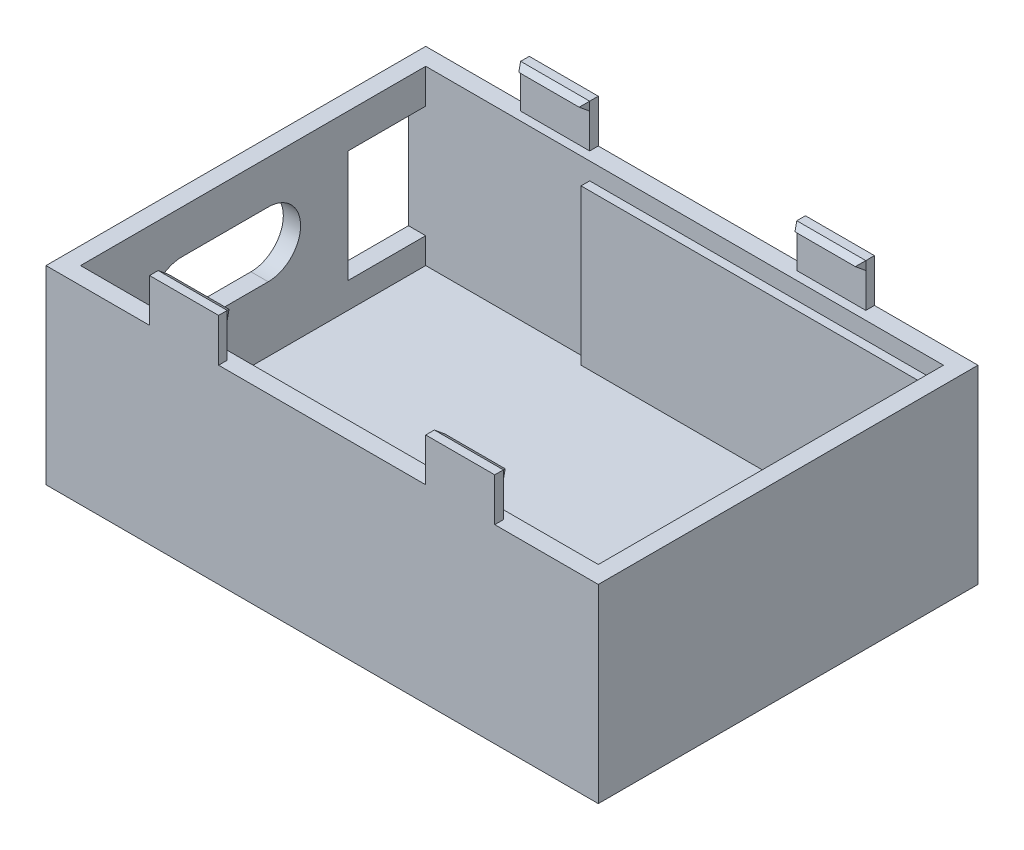
SolidWorks part; units mm, degrees
ref_plane "Front Plane" through (0, 0, 0) normal (0, 0, 1) x (1, 0, 0)
ref_plane "Top Plane" through (0, 0, 0) normal (0, 1, 0) x (1, 0, 0)
ref_plane "Right Plane" through (0, 0, 0) normal (1, 0, 0) x (0, 0, -1)
sketch "Sketch3" plane through (0, 0, 0) normal (0, 1, 0) x (1, 0, 0)
  line L9 (-32, 22) -> (32, 22)
  line L10 (-32, 22) -> (-32, -22)
  line L11 (-32, -22) -> (32, -22)
  line L12 (32, 22) -> (32, -22)
  line L13 (-32, 22) -> (32, -22) construction
  line L14 (-32, -22) -> (32, 22) construction
  line L15 (-30, 20) -> (-11, 20)
  line L16 (-30, 20) -> (-30, -20)
  line L17 (-30, -20) -> (29, -20)
  line L19 (-30, 20) -> (29, -19.3333) construction
  line L20 (-30, -20) -> (29.0678, 19.3785) construction
  line L22 (-11, 20) -> (-11, 19)
  line L23 (-11, 19) -> (29, 19)
  line L25 (-11, 20) -> (29.0678, 19.3785) construction
  line L26 (-11, 19) -> (29.0637, 19.9813) construction
  line L27 (29, 19) -> (29, -20)
  point P0 (0, 0)
  point P5 (0, 0)
  point P10 (0, 0)
  point P11 (0, 0)
  point P15 (13.9975, 19.6123)
  dimension "D1" = 3
  dimension "D2" = 40
  dimension "D3" = 64
  dimension "D4" = 44
  dimension "D5" = 1
  dimension "D6" = 40
  dimension "D7" = 59
extrude "Boss-Extrude1" add sketch "Sketch3" along normal blind 22
extrude "Boss-Extrude2" add sketch "Sketch3<2>" along normal blind 2 contours L15 L16 L17 region at (-0.6638, 0, 0.3362)
sketch "Sketch3<2>" plane through (0, 0, 0) normal (0, 1, 0) x (1, 0, 0) same geometry as "Sketch3"
sketch "Sketch5" plane through (0, 22, 0) normal (0, 1, 0) x (1, 0, 0)
  line L0 (-30, -20) -> (29, -20) construction
  line L1 (-30, 20) -> (30, 20)
  line L2 (-30, 20) -> (-30, -20)
  line L3 (-30, -20) -> (30, -20)
  line L4 (30, 20) -> (30, -20)
  line L5 (-30, 20) -> (30, -20) construction
  line L6 (-30, -20) -> (30, 20) construction
  line L7 (-30, 20) -> (-30, -20) construction
  point P0 (0, 0)
  dimension "D1" = 60
extrude "Cut-Extrude1" cut sketch "Sketch5" against normal blind 2
sketch "Sketch6" plane through (-32, 0, 0) normal (-1, 0, 0) x (0, 0, 1)
  line L0 (-22, 22) -> (-22, 0) construction
  line L1 (-20, 18) -> (-11, 18)
  line L2 (-20, 18) -> (-20, 5)
  line L3 (-20, 5) -> (-11, 5)
  line L4 (-11, 18) -> (-11, 5)
  line L5 (-20, 18) -> (-11, 5) construction
  line L6 (-20, 5) -> (-11, 18) construction
  line L7 (-22, 22) -> (22, 22) construction
  point P0 (-15.5, 11.5)
  dimension "D1" = 2
  dimension "D2" = 9
  dimension "D3" = 13
  dimension "D4" = 4
extrude "sw" cut sketch "Sketch6" against normal blind 2
sketch "Sketch8" plane through (-32, 0, 0) normal (-1, 0, 0) x (0, 0, 1)
  line L0 (-1.75, 13.25) -> (8.25, 13.25) construction
  line L1 (-1.75, 17) -> (8.25, 17)
  line L2 (-1.75, 9.5) -> (8.25, 9.5)
  line L3 (-22, 22) -> (22, 22) construction
  line L5 (22, 22) -> (22, 0) construction
  arc A0 (-1.75, 17) -> (-1.75, 9.5) centre (-1.75, 13.25) ccw
  arc A1 (8.25, 9.5) -> (8.25, 17) centre (8.25, 13.25) ccw
  point P2 (3.25, 13.25)
  dimension "D3" = 10
  dimension "D1" = 5
  dimension "D2" = 7.5
  dimension "D4" = 13.75
extrude "Cut-Extrude3" cut sketch "Sketch8" against normal blind 2
sketch "Sketch10" plane through (0, 22, 0) normal (0, 1, 0) x (1, 0, 0)
  line L0 (32, 22) -> (-32, 22) construction
  line L1 (-20, 22) -> (-12, 22)
  line L2 (-20, 22) -> (-20, 21)
  line L3 (-20, 21) -> (-12, 21)
  line L4 (-12, 22) -> (-12, 21)
  line L5 (-20, 22) -> (-12, 21) construction
  line L6 (-20, 21) -> (-12, 22) construction
  line L7 (-32, 22) -> (-32, -22) construction
  line L8 (-12.1, 0) -> (12.1, 0) construction
  line L9 (-20, -21) -> (-12, -22) construction
  line L10 (-20, -22) -> (-12, -21) construction
  line L11 (-12, -22) -> (-12, -21)
  line L12 (-20, -21) -> (-12, -21)
  line L13 (-20, -22) -> (-20, -21)
  line L14 (-20, -22) -> (-12, -22)
  line L15 (0, -12.1) -> (0, 12.1) construction
  line L16 (20, -22) -> (12, -21) construction
  line L17 (20, -21) -> (12, -22) construction
  line L18 (20, 21) -> (12, 22) construction
  line L19 (20, 22) -> (12, 21) construction
  line L20 (20, -22) -> (12, -22)
  line L21 (20, -22) -> (20, -21)
  line L22 (20, -21) -> (12, -21)
  line L23 (12, -22) -> (12, -21)
  line L24 (12, 22) -> (12, 21)
  line L25 (20, 21) -> (12, 21)
  line L26 (20, 22) -> (20, 21)
  line L27 (20, 22) -> (12, 22)
  point P0 (-16, 21.5)
  point P15 (-16, -21.5)
  point P26 (16, -21.5)
  point P27 (16, 21.5)
  dimension "D1" = 1
  dimension "D2" = 8
  dimension "16" = 16
extrude "Boss-Extrude3" add sketch "Sketch10" along normal blind 5
sketch "Sketch13" plane through (0, 0, 21) normal (0, 0, -1) x (-1, 0, 0)
  line L0 (12, 27) -> (20, 27) construction
  line L1 (12, 27) -> (20, 27)
  line L2 (12, 27) -> (12, 26)
  line L3 (12, 26) -> (20, 26)
  line L4 (20, 27) -> (20, 26)
  line L5 (12, 27) -> (20, 26) construction
  line L6 (12, 26) -> (20, 27) construction
  line L7 (12, 27) -> (12, 22) construction
  line L8 (0, 14.85) -> (0, -14.85) construction
  line L9 (-12, 26) -> (-20, 27) construction
  line L10 (-12, 27) -> (-20, 26) construction
  line L11 (-20, 27) -> (-20, 26)
  line L12 (-12, 26) -> (-20, 26)
  line L13 (-12, 27) -> (-12, 26)
  line L14 (-12, 27) -> (-20, 27)
  point P0 (16, 26.5)
  point P15 (-16, 26.5)
  dimension "D1" = 1
extrude "Boss-Extrude4" add sketch "Sketch13" along normal blind 1 draft 35
mirror "Mirror1" about plane through (0, 0, 0) normal (0, 0, 1) of "Boss-Extrude4"
